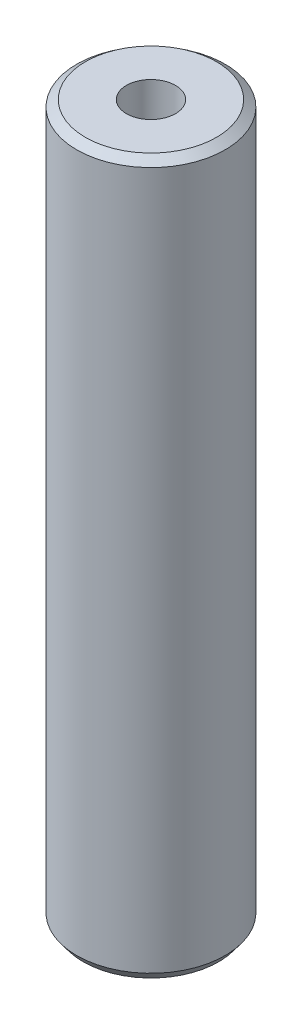
SolidWorks part; units mm, degrees
ref_plane "Front Plane" through (0, 0, 0) normal (0, 0, 1) x (1, 0, 0)
ref_plane "Top Plane" through (0, 0, 0) normal (0, 1, 0) x (1, 0, 0)
ref_plane "Right Plane" through (0, 0, 0) normal (1, 0, 0) x (0, 0, -1)
sketch "Sketch1" plane through (0, 0, 0) normal (0, 1, 0) x (1, 0, 0)
  circle A0 centre (0, 0) radius 7.5
  dimension "SHAFT_OD" = 15
extrude "Boss-Extrude1" add sketch "Sketch1" along normal blind 72.0262
sketch "Sketch2" plane through (0, 0, 0) normal (0, 1, 0) x (1, 0, 0)
  circle A0 centre (0, 0) radius 2.4797
  dimension "BORE_D" = 4.9595
extrude "Cut-Extrude1" cut sketch "Sketch2" along normal through all
chamfer "Chamfer1" distance 0.6532 angle 53.266 2 edges at (0, 72.0262, 7.5) (0, 0, 7.5) first distance on face at (0, 72.0262, 7.5) first distance on face at (0, 0, 2.4797)
